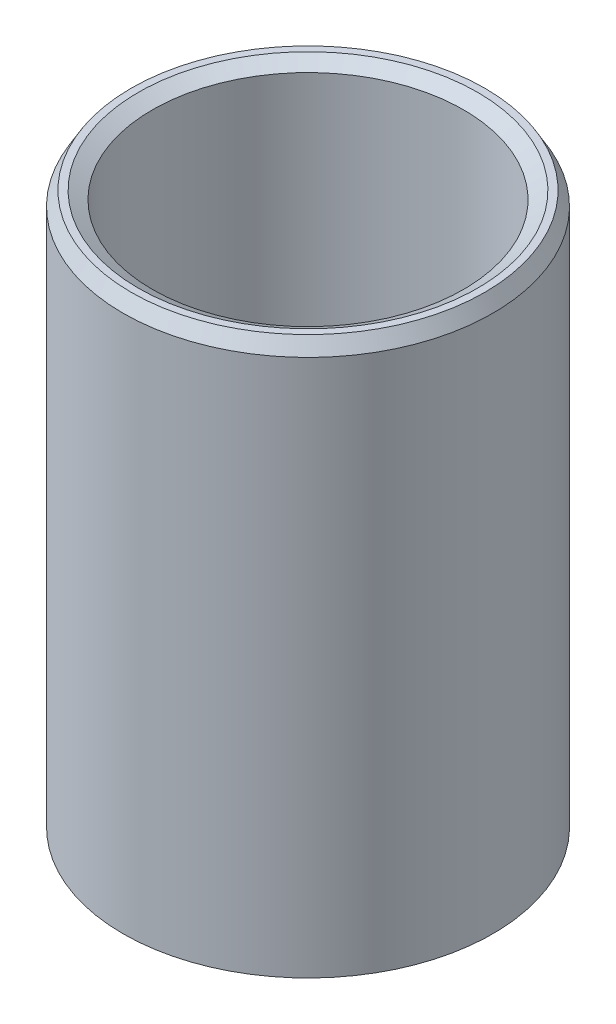
SolidWorks part; units mm, degrees
ref_plane "Front Plane" through (0, 0, 0) normal (0, 0, 1) x (1, 0, 0)
ref_plane "Top Plane" through (0, 0, 0) normal (0, 1, 0) x (1, 0, 0)
ref_plane "Right Plane" through (0, 0, 0) normal (1, 0, 0) x (0, 0, -1)
sketch "Sketch1" plane through (0, 0, 0) normal (0, 1, 0) x (1, 0, 0)
  circle A0 centre (0, 0) radius 22.5
  dimension "SLEEVE_OD" = 45
extrude "Boss-Extrude1" add sketch "Sketch1" along normal blind 68.0839
sketch "Sketch2" plane through (0, 0, 0) normal (0, 1, 0) x (1, 0, 0)
  circle A0 centre (0, 0) radius 18.9339
  dimension "BORE_D" = 37.8678
extrude "Cut-Extrude1" cut sketch "Sketch2" along normal through all
chamfer "Chamfer1" distance 1.7085 angle 30 4 edges at (0, 68.0839, 18.9339) (0, 0, 18.9339) (0, 0, 22.5) (0, 68.0839, 22.5) first distance on face at (0, 68.0839, 18.9339) first distance on face at (0, 0, 18.9339) first distance on face at (0, 68.0839, 22.5)
